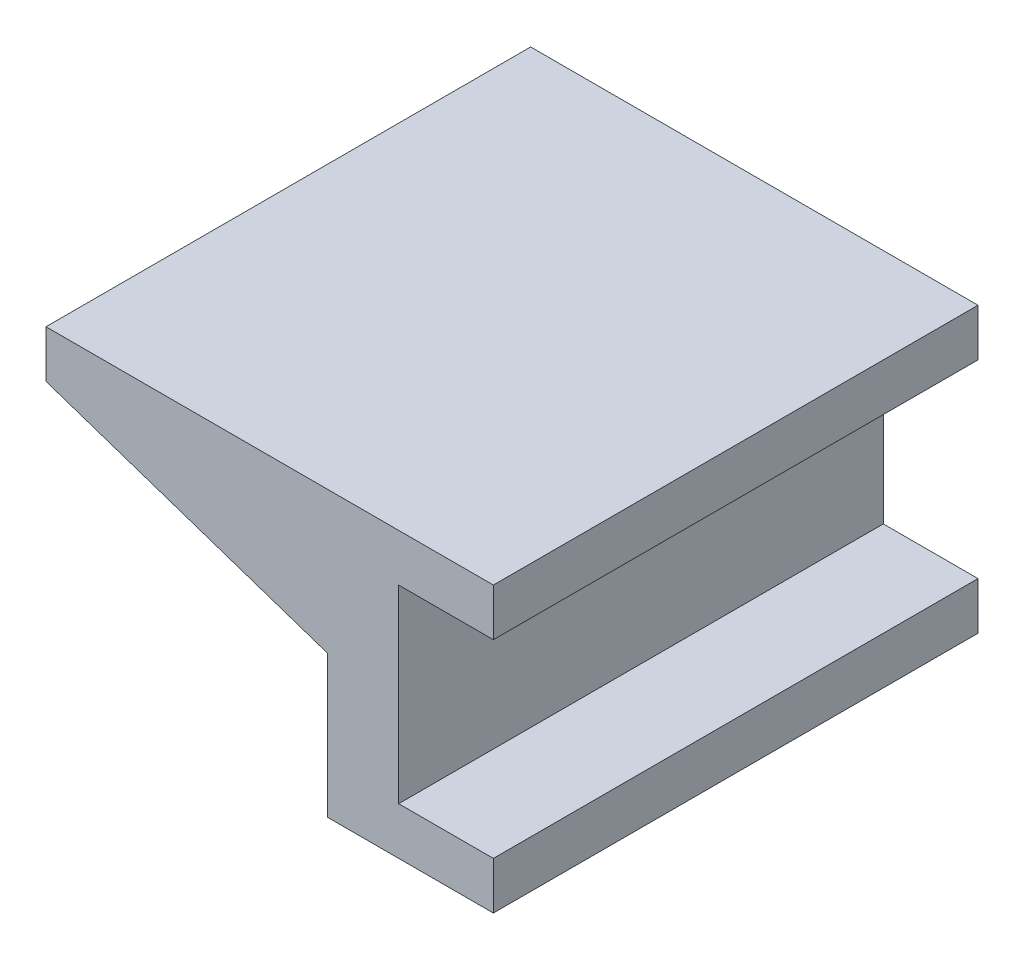
SolidWorks part; units mm, degrees
material "Choose your Material"
ref_plane "Front Plane" through (0, 0, 0) normal (0, 0, 1) x (1, 0, 0)
ref_plane "Top Plane" through (0, 0, 0) normal (0, 1, 0) x (1, 0, 0)
ref_plane "Right Plane" through (0, 0, 0) normal (1, 0, 0) x (0, 0, -1)
sketch "Sketch1" plane through (0, 0, 0) normal (0, 0, 1) x (1, 0, 0)
  line L0 (44.45, 12.7) -> (-75.55, 12.7)
  line L2 (0, -63.5) -> (0, -25.4)
  line L4 (19.05, -50.8) -> (19.05, 0)
  line L5 (19.05, 0) -> (44.45, 0)
  line L8 (44.45, 0) -> (44.45, 12.7)
  line L9 (19.05, -50.8) -> (44.45, -50.8)
  line L11 (0, -63.5) -> (44.45, -63.5)
  line L12 (44.45, -50.8) -> (44.45, -63.5)
  line L13 (-75.55, 12.7) -> (-75.55, 0)
  line L14 (-75.55, 0) -> (0, -25.4)
  line L15 (0, -25.4) -> (19.05, -25.4) construction
  point P0 (23.2884, 0)
  point P13 (0, 0)
  point P14 (0, 0)
  point P15 (-42.547, 0)
  point P16 (0, -25.4)
  dimension "D1" = 50.8
  dimension "D2" = 25.4
  dimension "D3" = 12.7
  dimension "D4" = 12.7
  dimension "D5" = 120
  dimension "D6" = 19.05
extrude "Boss-Extrude1" add sketch "Sketch1" along normal mid plane 130
